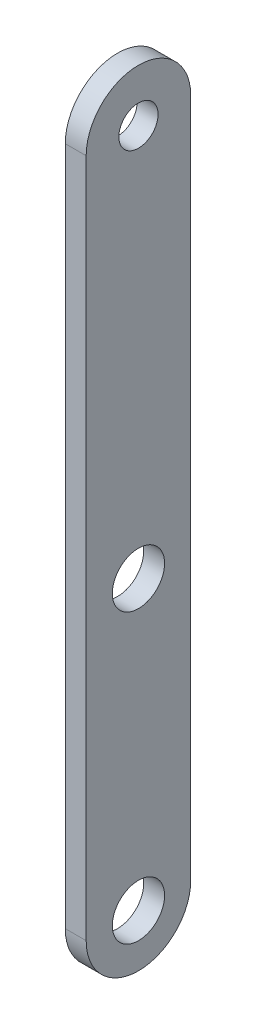
SolidWorks part; units mm, degrees
ref_plane "Front Plane" through (0, 0, 0) normal (0, 0, 1) x (1, 0, 0)
ref_plane "Top Plane" through (0, 0, 0) normal (0, 1, 0) x (1, 0, 0)
ref_plane "Right Plane" through (0, 0, 0) normal (1, 0, 0) x (0, 0, -1)
sketch "Sketch2" plane through (0, 0, 0) normal (1, 0, 0) x (0, 0, -1)
  line L0 (-20, 0) -> (20, 0) construction
  line L1 (-20, 0) -> (-20, -260)
  line L2 (20, 0) -> (20, -260)
  line L3 (0, 0) -> (0, 7.5) construction
  line L11 (-20, -260) -> (20, -260) construction
  line L12 (0, 0) -> (0, -150) construction
  circle A0 centre (0, 0) radius 7.5
  arc A1 (-20, 0) -> (20, 0) centre (0, 0) cw
  circle A2 centre (0, -150) radius 10
  arc A3 (-20, -260) -> (20, -260) centre (0, -260) ccw
  circle A4 centre (0, -260) radius 10
  dimension "D1" = 15
  dimension "D7" = 20
  dimension "D8" = 20
  dimension "D2" = 40
  dimension "D3" = 260
  dimension "D6" = 150
extrude "Boss-Extrude1" add sketch "Sketch2" along normal blind 4 and the other way blind 4 contours L1 A3 L2 A1 A0 A2 region at (0, -127.7744, 0)
